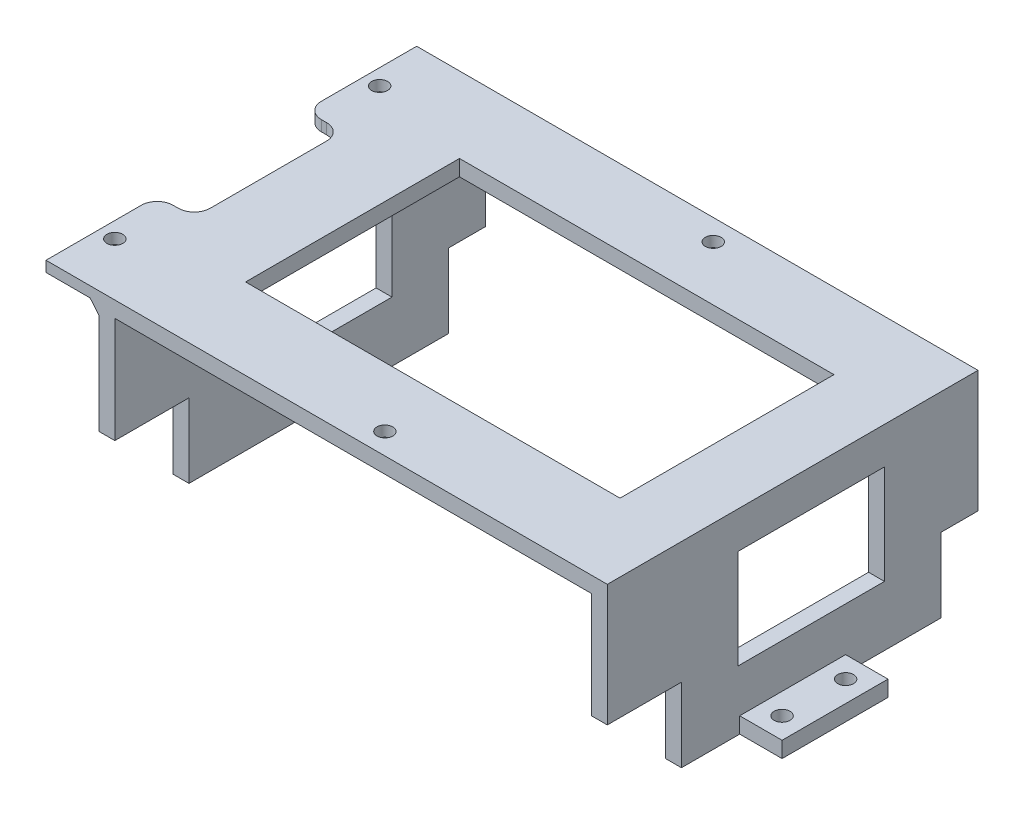
SolidWorks part; units mm, degrees
ref_plane "前视基准面" through (0, 0, 0) normal (0, 0, 1) x (1, 0, 0)
ref_plane "上视基准面" through (0, 0, 0) normal (0, 1, 0) x (1, 0, 0)
ref_plane "右视基准面" through (0, 0, 0) normal (1, 0, 0) x (0, 0, -1)
other "Configuration Table"
sketch "草图1" plane through (0, 0, 0) normal (0, 1, 0) x (1, 0, 0)
  line L1 (-45, -35) -> (45, -35)
  line L2 (-45, -35) -> (-45, 35)
  line L3 (-45, 35) -> (45, 35)
  line L4 (45, -35) -> (45, 35)
  line L5 (-45, -35) -> (45, 35) construction
  line L6 (-45, 35) -> (45, -35) construction
  line L7 (-45, 35) -> (-48, 35)
  line L8 (-45, 35) -> (-45, -35)
  line L9 (-45, -35) -> (-48, -35)
  line L10 (-48, 35) -> (-48, -35)
  line L11 (45, -35) -> (48, -35)
  line L12 (45, -35) -> (45, 35)
  line L13 (45, 35) -> (48, 35)
  line L14 (48, -35) -> (48, 35)
  point P0 (0, 0)
  dimension "D1" = 90
  dimension "D2" = 70
  dimension "D3" = 3
  dimension "D4" = 3
extrude "凸台-拉伸1" add sketch "草图1" along normal blind 3 contours L7 L10 L9 L2 | L1 L4 L3 L2 | L11 L14 L13 L4 region at (0, 0, 0) region at (-46.5, 0, 0) region at (46.5, 0, 0)
extrude "凸台-拉伸2" add sketch "草图1<3>" against normal blind 34 contours L7 L10 L9 L2 | L11 L14 L13 L4 region at (-46.5, 0, 0) region at (46.5, 0, 0)
sketch "草图1<3>" plane through (0, 0, 0) normal (0, 1, 0) x (1, 0, 0) same geometry as "草图1"
sketch "草图2" plane through (-48, 0, 0) normal (-1, 0, 0) x (0, 0, 1)
  line L1 (-10, -34) -> (10, -34)
  line L2 (-10, -34) -> (-10, -31)
  line L3 (-10, -31) -> (10, -31)
  line L4 (-35, 3) -> (-35, -34)
  line L5 (-35, -34) -> (35, -34)
  line L6 (35, -34) -> (35, 3)
  line L7 (35, 3) -> (-35, 3)
  line L8 (-35, 3) -> (-35, -34)
  line L9 (-35, -34) -> (35, -34)
  line L10 (35, -34) -> (35, 3)
  line L11 (35, 3) -> (-35, 3)
  line L12 (10, -34) -> (10, -31)
  point P8 (0, -34)
  point P9 (0, -34)
  dimension "D2" = 3
  dimension "D3" = 20
  dimension "D1" = 0
extrude "凸台-拉伸3" add sketch "草图2" along normal blind 8 contours L3 L12 L1 L2
mirror "镜向1" about plane through (0, 0, 0) normal (1, 0, 0) of "凸台-拉伸3"
sketch "草图3" plane through (0, -31, 0) normal (0, 1, 0) x (1, 0, 0)
  line L0 (-48, 0) -> (-56, 0) construction
  line L4 (-48, -10) -> (-48, 10)
  line L5 (-48, 10) -> (-56, 10)
  line L6 (-56, 10) -> (-56, -10)
  line L7 (-56, -10) -> (-48, -10)
  line L8 (-48, -10) -> (-48, 10)
  line L9 (-48, 10) -> (-56, 10)
  line L10 (-56, 10) -> (-56, -10)
  line L11 (-56, -10) -> (-48, -10)
  circle A0 centre (-52, 6) radius 1.5
  circle A1 centre (-52, -6) radius 1.5
  dimension "D2" = 3
  dimension "D3" = 12
  dimension "D4" = 4
  dimension "D1" = 0
extrude "切除-拉伸1" cut sketch "草图3" against normal blind 8 contours A0 | A1 region at (-52, -31, -6) region at (-52, -31, 6)
mirror "镜向3" about plane through (0, 0, 0) normal (1, 0, 0) of "切除-拉伸1"
sketch "草图4" plane through (0, 3, 0) normal (0, 1, 0) x (1, 0, 0)
  line L0 (48, 0) -> (-48, 0) construction
  line L1 (48, -35) -> (48, 35) construction
  line L2 (-48, 35) -> (-48, -35) construction
  circle A0 centre (-55, 25) radius 1.5
  circle A1 centre (-55, -25) radius 1.5
  circle A2 centre (2, 31) radius 1.5
  circle A3 centre (2, -31) radius 1.5
  dimension "D1" = 3
  dimension "D2" = 3
  dimension "D3" = 50
  dimension "D4" = 62
  dimension "D5" = 57
  dimension "D6" = 7
sketch "草图5" plane through (-48, 0, 0) normal (-1, 0, 0) x (0, 0, 1)
  line L0 (35, 3) -> (35, -34) construction
  line L1 (-35, 3) -> (35, 3)
  line L2 (-35, 3) -> (-35, 1)
  line L3 (-35, 1) -> (35, 1)
  line L4 (35, 3) -> (35, 1)
  dimension "D1" = 2
extrude "凸台-拉伸4" add sketch "草图5" along normal blind 10
extrude "切除-拉伸2" cut sketch "草图4" against normal up to surface (2 mm away) up to face at (-53, 1, 0)
sketch "草图6" plane through (0, 3, 0) normal (0, 1, 0) x (1, 0, 0)
  line L0 (-58, 0) -> (-50.6784, 0) construction
  line L1 (-58, -35) -> (-58, 35) construction
  line L3 (-58, -14) -> (-51, -14)
  line L4 (-58, -14) -> (-58, 14)
  line L5 (-58, 14) -> (-51, 14)
  line L6 (-51, -14) -> (-51, 14)
  point P9 (-58, 0)
  dimension "D1" = 7
  dimension "D2" = 28
extrude "切除-拉伸3" cut sketch "草图6" against normal up to surface (2 mm away) up to face at (-55, 1, 26.5)
fillet "圆角1" radius 3 4 edges at (-58, 2, -14) (-58, 2, 14) (-51, 2, 14) (-51, 2, -14)
sketch "草图7" plane through (45, 0, 0) normal (-1, 0, 0) x (0, 0, 1)
  line L1 (35, -34) -> (21, -34)
  line L2 (35, -34) -> (35, -20)
  line L3 (35, -20) -> (21, -20)
  line L4 (21, -34) -> (21, -20)
  line L5 (-35, -34) -> (-28, -34)
  line L6 (-35, -34) -> (-35, -20)
  line L7 (-35, -20) -> (-28, -20)
  line L8 (-28, -34) -> (-28, -20)
  dimension "D1" = 14
  dimension "D2" = 14
  dimension "D3" = 7
  dimension "D4" = 14
extrude "切除-拉伸4" cut sketch "草图7" against normal up to surface (3 mm away) up to face at (48, -24, 0)
sketch "草图8" plane through (-48, 0, 0) normal (-1, 0, 0) x (0, 0, 1)
  line L0 (35, 1) -> (35, -34) construction
  line L1 (35, -34) -> (21, -34)
  line L2 (35, -34) -> (35, -20)
  line L3 (35, -20) -> (21, -20)
  line L4 (21, -34) -> (21, -20)
  line L5 (10, -34) -> (35, -34) construction
  line L8 (-35, -34) -> (-28, -34)
  line L9 (-35, -34) -> (-35, -20)
  line L10 (-35, -20) -> (-28, -20)
  line L11 (-28, -34) -> (-28, -20)
  dimension "D1" = 14
  dimension "D2" = 14
  dimension "D3" = 14
  dimension "D4" = 7
extrude "切除-拉伸5" cut sketch "草图8" against normal up to surface (3 mm away) up to face at (-45, -17, 0)
sketch "草图9" plane through (0, 3, 0) normal (0, 1, 0) x (1, 0, 0)
  line L1 (35.1069, -19.7071) -> (-35.6068, -19.7071)
  line L2 (35.1069, -19.7071) -> (35.1069, 20.6894)
  line L3 (35.1069, 20.6894) -> (-35.6068, 20.6894)
  line L4 (-35.6068, -19.7071) -> (-35.6068, 20.6894)
extrude "切除-拉伸6" cut sketch "草图9" against normal up to surface (3 mm away) up to face at (0, 0, 0)
sketch "草图10" plane through (-48, 0, 0) normal (-1, 0, 0) x (0, 0, 1)
  line L1 (-17.3361, -3.9595) -> (10.333, -3.9595)
  line L2 (-17.3361, -3.9595) -> (-17.3361, -22.6922)
  line L3 (-17.3361, -22.6922) -> (10.333, -22.6922)
  line L4 (10.333, -3.9595) -> (10.333, -22.6922)
extrude "切除-拉伸7" cut sketch "草图10" against normal up to surface (96 mm away) up to face at (48, -22.6667, -1.1667)
chamfer "倒角1" distance 2 angle 40 1 edges at (-48, 1, 0) first distance on face at (-48, -13.3259, -3.5016)
